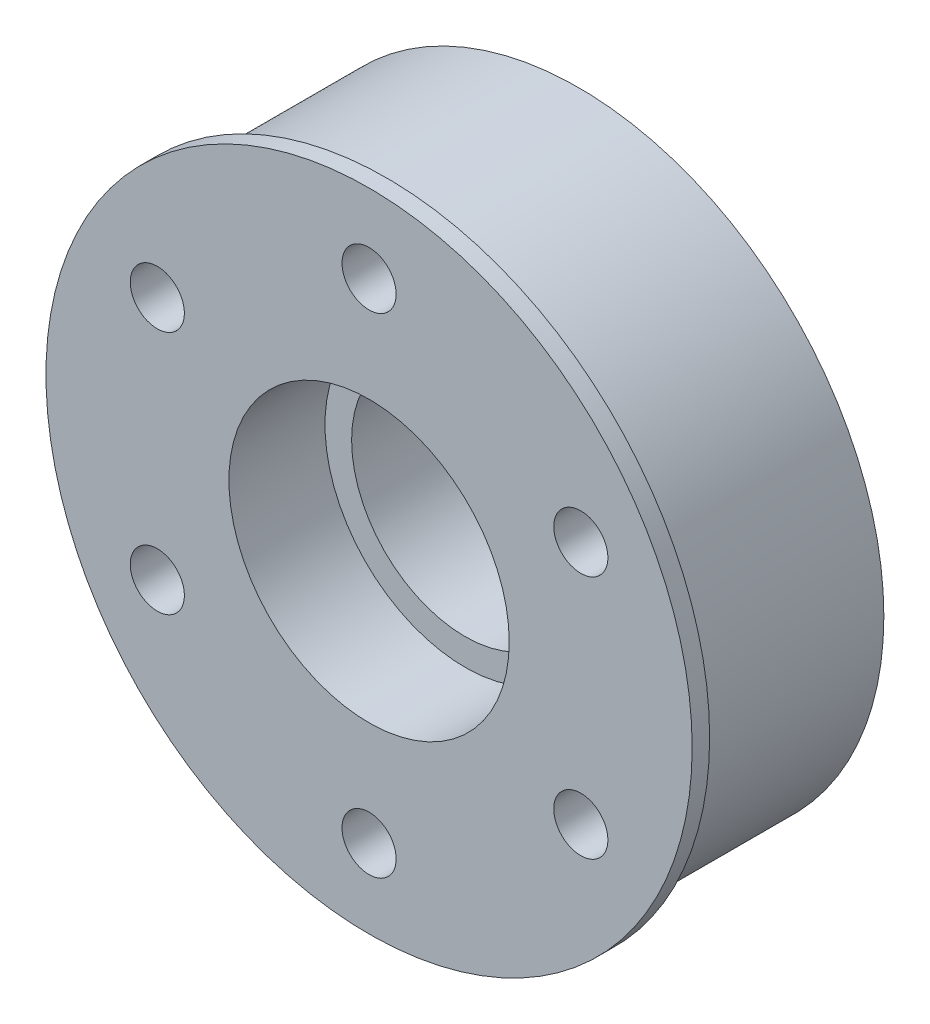
SolidWorks part; units mm, degrees
material "6061 Alloy"
ref_plane "Front Plane" through (0, 0, 0) normal (0, 0, 1) x (1, 0, 0)
ref_plane "Top Plane" through (0, 0, 0) normal (0, 1, 0) x (1, 0, 0)
ref_plane "Right Plane" through (0, 0, 0) normal (1, 0, 0) x (0, 0, -1)
sketch "Sketch1" plane through (0, 0, 0) normal (0, 0, 1) x (1, 0, 0)
  line L0 (0, 0) -> (0, 28.3945) construction
  circle A0 centre (0, 0) radius 8.025
  circle A1 centre (0, 0) radius 17.475
  circle A2 centre (0, 14) radius 1.55
  circle A3 centre (12.1244, 7) radius 1.55
  circle A4 centre (12.1244, -7) radius 1.55
  circle A5 centre (0, -14) radius 1.55
  circle A6 centre (-12.1244, -7) radius 1.55
  circle A7 centre (-12.1244, 7) radius 1.55
  circle A8 centre (0, 0) radius 18.5
  point P22 (0, 0)
  dimension "D1" = 34.95
  dimension "D2" = 16.05
  dimension "D3" = 3.1
  dimension "D6" = 37
  dimension "D4" = 14
  dimension "D5" = 6
extrude "Boss-Extrude1" add sketch "Sketch1" along normal blind 12 contours A7 | A6 | A5 | A4 | A3 | L0 A2 | A2 L0 | A0 A2 A1 A7 A6 A5 A4 A3 region at (12.0072, 12.0072, 0) region at (-0.6578, 14, 0) region at (0.6578, 14, 0) region at (12.1244, 7, 0) region at (12.1244, -7, 0) region at (0, -14, 0) region at (-12.1244, -7, 0) region at (-12.1244, 7, 0)
extrude "Cut-Extrude1" cut sketch "Sketch1<3>" against normal blind 4 from surface contours A7 | A2 L0 | L0 A2 | A3 | A4 | A5 | A6 region at (-0.6578, 14, 0) region at (0.6578, 14, 0) region at (12.1244, 7, 0) region at (12.1244, -7, 0) region at (0, -14, 0) region at (-12.1244, -7, 0) region at (-12.1244, 7, 0) starting at face at (17.475, 0, 12)
sketch "Sketch1<3>" plane through (0, 0, 0) normal (0, 0, 1) x (1, 0, 0) same geometry as "Sketch1"
extrude "Boss-Extrude2" add sketch "Sketch1<4>" against normal blind 1 from surface contours A1 A8 region at (-17.9767, 0, 0) starting at face at (-10.5744, -7, 12)
sketch "Sketch1<4>" plane through (0, 0, 0) normal (0, 0, 1) x (1, 0, 0) same geometry as "Sketch1"
sketch "Sketch2" plane through (0, 0, 0) normal (0, 0, -1) x (-1, 0, 0)
  circle A0 centre (0, 0) radius 6.5
  circle A1 centre (0, 0) radius 8.025
  dimension "D1" = 13
  dimension "D2" = 16.05
extrude "Boss-Extrude3" add sketch "Sketch2" against normal up to surface (12 mm away) up to face at (-10.5744, -7, 12)
extrude "Cut-Extrude2" cut sketch "Sketch2<2>" along normal blind 5.5 from surface starting at face at (-10.5744, -7, 12)
sketch "Sketch2<2>" plane through (0, 0, 0) normal (0, 0, -1) x (-1, 0, 0) same geometry as "Sketch2"
sketch "Sketch3" plane through (0, 0, 0) normal (0, 0, 1) x (1, 0, 0)
  line L0 (0, 0) -> (0, 19.5698) construction
  line L1 (0, 0) -> (-10.0099, 17.3376) construction
  circle A0 centre (0, 0) radius 12 construction
  circle A1 centre (-6, 10.3923) radius 2.5
  circle A2 centre (6, 10.3923) radius 2.5
  circle A3 centre (12, 0) radius 2.5
  circle A4 centre (6, -10.3923) radius 2.5
  circle A5 centre (-6, -10.3923) radius 2.5
  circle A6 centre (-12, 0) radius 2.5
  point P20 (0, 0)
  dimension "D1" = 24
  dimension "D2" = 5
  dimension "D3" = 30
  dimension "D4" = 6
hole_wizard "M5 Tapped Hole1" positions "Sketch4" profile "Sketch5" tap size "M5" standard "ISO"
sketch "Sketch4" plane through (0, 0, 0) normal (0, 0, -1) x (-1, 0, 0)
  point P0 (-12, 0)
  point P3 (-6, -10.3923)
  point P6 (6, -10.3923)
  point P9 (6, 10.3923)
  point P12 (12, 0)
  point P15 (-6, 10.3923)
sketch "Sketch5" plane through (12, 0, 0) normal (1, 0, 0) x (0, 1, 0)
  line L0 (0, 0) -> (0, 9.2618)
  line L1 (0, 9.2618) -> (2.1, 8)
  line L2 (2.1, 8) -> (2.1, 0)
  line L5 (2.1, 0) -> (0, 0)
  line L10 (0, 9.2618) -> (-2.1, 8) construction
  line L11 (0, -6.35) -> (0, 107.95) construction
  dimension "Tap Drill Dia." = 4.2
  dimension "Tap Drill Depth" = 8
  dimension "Drill Angle" = 118
cosmetic thread "Hole Thread1" parameters "D1"=10, "D2"=5
cosmetic thread "Hole Thread2" parameters "D1"=10, "D2"=5
cosmetic thread "Hole Thread3" parameters "D1"=10, "D2"=5
cosmetic thread "Hole Thread4" parameters "D1"=10, "D2"=5
cosmetic thread "Hole Thread5" parameters "D1"=10, "D2"=5
cosmetic thread "Hole Thread6" parameters "D1"=10, "D2"=5
